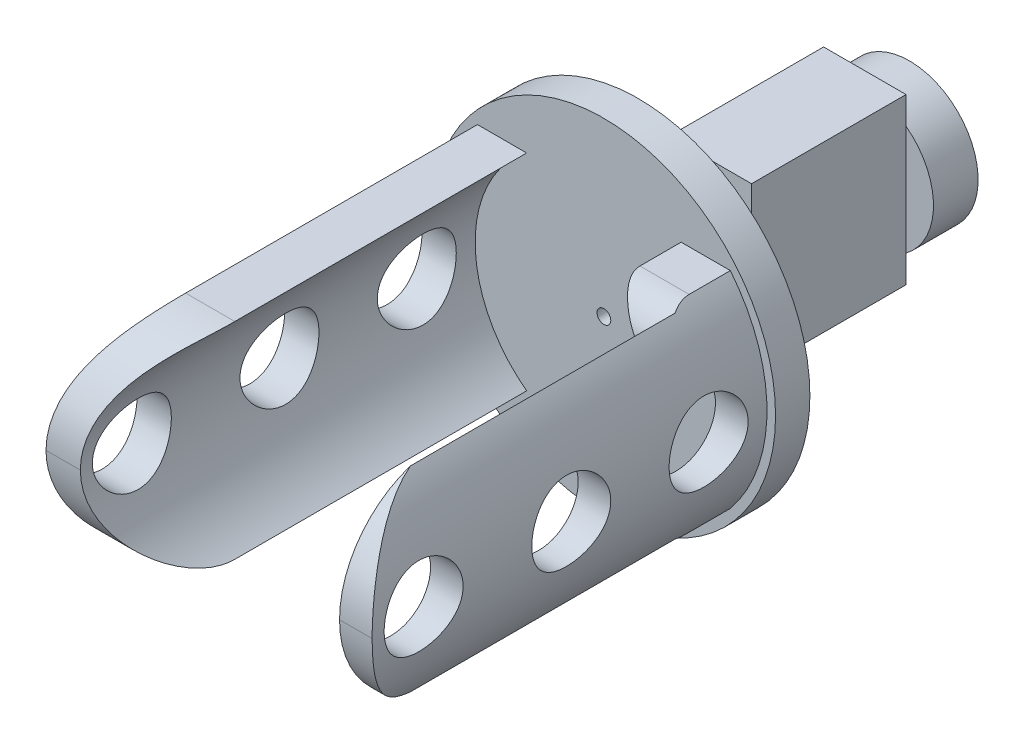
SolidWorks part; units mm, degrees
ref_plane "Plan de face" through (0, 0, 0) normal (0, 0, 1) x (1, 0, 0)
ref_plane "Plan de dessus" through (0, 0, 0) normal (0, 1, 0) x (1, 0, 0)
ref_plane "Plan de droite" through (0, 0, 0) normal (1, 0, 0) x (0, 0, -1)
sketch "Esquisse1" plane through (0, 0, 0) normal (0, 0, 1) x (1, 0, 0)
  circle A0 centre (0, 0) radius 50
  dimension "D1" = 100
extrude "Boss.-Extru.1" add sketch "Esquisse1" along normal blind 10
sketch "Esquisse2" plane through (0, 0, 0) normal (0, 0, -1) x (-1, 0, 0)
  circle A0 centre (0, 0) radius 47.5
  dimension "D1" = 95
extrude "Enlèv. mat.-Extru.1" cut sketch "Esquisse2" against normal blind 5
sketch "Esquisse6" plane through (0, 0, 10) normal (0, 0, 1) x (1, 0, 0)
  line L0 (0, 0) -> (0, 47.5) construction
  line L1 (0, 47.5) -> (0, -47.5) construction
  line L2 (-22.5, 30) -> (-22.5, -30) construction
  line L3 (-22.5, 30) -> (-36.8273, 30)
  line L4 (-22.5, -30) -> (-36.8273, -30)
  line L5 (22.5, -30) -> (36.8273, -30)
  line L6 (22.5, 30) -> (36.8273, 30)
  circle A0 centre (0, 0) radius 2
  circle A1 centre (0, 0) radius 47.5
  circle A2 centre (0, 0) radius 37.5
  circle A3 centre (0, 0) radius 50 construction
  dimension "D1" = 4
  dimension "D2" = 2.5
  dimension "D3" = 10
  dimension "D4" = 60
extrude "Boss.-Extru.4" add sketch "Esquisse6" along normal blind 115 contours A2 L3 A1 L4 | A2 L5 A1 L6 region at (-38.1648, 0, 10) region at (38.1648, 0, 10)
sketch "Esquisse7" plane through (0, 0, 5) normal (0, 0, -1) x (-1, 0, 0)
  circle A0 centre (0, 0) radius 2
  dimension "D1" = 4
extrude "Enlèv. mat.-Extru.2" cut sketch "Esquisse7" against normal blind 100
sketch "Esquisse12" plane through (0, 0, 10) normal (0, 0, 1) x (1, 0, 0)
  line L1 (-3.6437, 25.162) -> (0, 25.162)
  line L2 (-3.6437, 25.162) -> (-3.6437, 15.1247)
  line L3 (-3.6437, 15.1247) -> (0, 15.1247)
  line L4 (0, 25.162) -> (0, 15.1247)
extrude "Boss.-Extru.7" add sketch "Esquisse12" along normal blind 116
sketch "Esquisse14" plane through (0, 0, 0) normal (1, 0, 0) x (0, 0, -1)
  line L0 (-125, 0) -> (-10, 0) construction
  line L1 (-125, 30) -> (-125, -30) construction
  line L2 (-10, 50) -> (-10, -50) construction
  circle A0 centre (-110, 0) radius 11.5
  circle A2 centre (-67, 0) radius 11.5
  circle A3 centre (-27, 0) radius 11.5
  dimension "D4" = 23
  dimension "D5" = 23
  dimension "D6" = 23
  dimension "D1" = 100
  dimension "D2" = 17
  dimension "D3" = 40
extrude "Enlèv. mat.-Extru.3" cut sketch "Esquisse14" against normal through all both and the other way through all
sketch "Esquisse15" plane through (0, 0, 126) normal (0, 0, 1) x (1, 0, 0)
  line L1 (0, 15.1247) -> (-3.6437, 15.1247)
  line L2 (0, 15.1247) -> (0, 25.162)
  line L3 (0, 25.162) -> (-3.6437, 25.162)
  line L4 (-3.6437, 15.1247) -> (-3.6437, 25.162)
extrude "Enlèv. mat.-Extru.4" cut sketch "Esquisse15" against normal blind 116
sketch "Esquisse16" plane through (0, 0, 5) normal (0, 0, -1) x (-1, 0, 0)
  circle A0 centre (0, 0) radius 20
  circle A1 centre (0, 0) radius 2
  dimension "D1" = 40
extrude "Boss.-Extru.8" add sketch "Esquisse16" along normal blind 16
sketch "Esquisse17" plane through (0, 0, -11) normal (0, 0, -1) x (-1, 0, 0)
  line L0 (0, 0) -> (0, 20) construction
  line L1 (0, 20) -> (0, -20) construction
  line L2 (0, 0) -> (20, 0) construction
  line L3 (20, 0) -> (-20, 0) construction
  line L4 (0, 20) -> (1.98, 14.8687)
  line L5 (0, 20) -> (-1.98, 14.8687)
  line L6 (-0.9649, 14.9689) -> (-3.9011, 19.6158)
  line L7 (-3.9011, 19.6158) -> (-4.8485, 14.1948)
  line L8 (-3.9011, 19.6158) -> (0, 0) construction
  line L9 (0, 0) -> (3.9011, -19.6158) construction
  line L10 (-7.6524, 18.4781) -> (0, 0) construction
  line L11 (-11.1097, 16.6305) -> (0, 0) construction
  line L12 (-14.1402, 14.1441) -> (0, 0) construction
  line L13 (0, 0) -> (-16.6275, 11.1143) construction
  line L14 (0, 0) -> (-18.476, 7.6575) construction
  line L15 (0, 0) -> (-19.6148, 3.9065) construction
  line L16 (-9.9008, 11.2683) -> (-11.1097, 16.6305)
  line L17 (-11.1097, 16.6305) -> (-6.6069, 13.4666)
  line L18 (-11.2656, 9.9039) -> (-16.6275, 11.1143)
  line L19 (-16.6275, 11.1143) -> (-13.4647, 6.6107)
  line L20 (-14.9687, 0.9691) -> (-19.6148, 3.9065)
  line L21 (-19.6148, 3.9065) -> (-14.1934, 4.8524)
  line L22 (-7.6524, 18.4781) -> (-3.8597, 14.4949)
  line L23 (-7.6524, 18.4781) -> (-7.5184, 12.9797)
  line L24 (-14.1402, 14.1441) -> (-9.1121, 11.9151)
  line L25 (-14.1402, 14.1441) -> (-11.9126, 9.1154)
  line L26 (-18.476, 7.6575) -> (-14.4938, 3.8637)
  line L27 (-18.476, 7.6575) -> (-12.9777, 7.522)
  line L28 (-20, 0) -> (-14.8675, 1.9891)
  line L29 (-20, 0) -> (-14.8675, -1.9891)
  line L30 (-14.9687, -0.9691) -> (-19.6148, -3.9065)
  line L31 (-19.6148, -3.9065) -> (-14.1934, -4.8524)
  line L32 (-18.476, -7.6575) -> (-14.4938, -3.8637)
  line L33 (-18.476, -7.6575) -> (-12.9777, -7.522)
  line L34 (-16.6275, -11.1143) -> (-13.4647, -6.6107)
  line L35 (-11.2656, -9.9039) -> (-16.6275, -11.1143)
  line L36 (-14.1402, -14.1441) -> (-11.9126, -9.1154)
  line L37 (-14.1402, -14.1441) -> (-9.1121, -11.9151)
  line L38 (-9.9008, -11.2683) -> (-11.1097, -16.6305)
  line L39 (-11.1097, -16.6305) -> (-6.6069, -13.4666)
  line L40 (-7.6524, -18.4781) -> (-7.5184, -12.9797)
  line L41 (-7.6524, -18.4781) -> (-3.8597, -14.4949)
  line L42 (-3.9011, -19.6158) -> (-4.8485, -14.1948)
  line L43 (-0.9649, -14.9689) -> (-3.9011, -19.6158)
  line L44 (0, -20) -> (-1.98, -14.8687)
  line L45 (0, -20) -> (1.98, -14.8687)
  line L46 (0.9649, -14.9689) -> (3.9011, -19.6158)
  line L47 (3.9011, -19.6158) -> (4.8485, -14.1948)
  line L48 (7.6524, -18.4781) -> (3.8597, -14.4949)
  line L49 (7.6524, -18.4781) -> (7.5184, -12.9797)
  line L50 (11.1097, -16.6305) -> (6.6069, -13.4666)
  line L51 (9.9008, -11.2683) -> (11.1097, -16.6305)
  line L52 (14.1402, -14.1441) -> (9.1121, -11.9151)
  line L53 (14.1402, -14.1441) -> (11.9126, -9.1154)
  line L54 (11.2656, -9.9039) -> (16.6275, -11.1143)
  line L55 (16.6275, -11.1143) -> (13.4647, -6.6107)
  line L56 (18.476, -7.6575) -> (12.9777, -7.522)
  line L57 (18.476, -7.6575) -> (14.4938, -3.8637)
  line L58 (19.6148, -3.9065) -> (14.1934, -4.8524)
  line L59 (14.9687, -0.9691) -> (19.6148, -3.9065)
  line L60 (20, 0) -> (14.8675, -1.9891)
  line L61 (20, 0) -> (14.8675, 1.9891)
  line L62 (14.9687, 0.9691) -> (19.6148, 3.9065)
  line L63 (19.6148, 3.9065) -> (14.1934, 4.8524)
  line L64 (18.476, 7.6575) -> (14.4938, 3.8637)
  line L65 (18.476, 7.6575) -> (12.9777, 7.522)
  line L66 (16.6275, 11.1143) -> (13.4647, 6.6107)
  line L67 (11.2656, 9.9039) -> (16.6275, 11.1143)
  line L68 (14.1402, 14.1441) -> (11.9126, 9.1154)
  line L69 (14.1402, 14.1441) -> (9.1121, 11.9151)
  line L70 (9.9008, 11.2683) -> (11.1097, 16.6305)
  line L71 (11.1097, 16.6305) -> (6.6069, 13.4666)
  line L72 (7.6524, 18.4781) -> (7.5184, 12.9797)
  line L73 (7.6524, 18.4781) -> (3.8597, 14.4949)
  line L74 (3.9011, 19.6158) -> (4.8485, 14.1948)
  line L75 (0.9649, 14.9689) -> (3.9011, 19.6158)
  line L76 (0, 20) -> (1.98, 14.8687)
  circle A0 centre (0, 0) radius 20
  circle A1 centre (0, 0) radius 2
  circle A2 centre (0, 0) radius 15
  circle M45 centre (0, 0) radius 20
  dimension "D4" = 1.98
  dimension "D5" = 3.96
  dimension "D6" = 1.02
  dimension "D8" = 1.02
extrude "Enlèv. mat.-Extru.7" cut sketch "Esquisse17" against normal blind 16 contours L30 L29 M45 | L32 L31 M45 | L34 L33 M45 | L36 L35 M45 | L38 L37 M45 | L40 L39 M45 | L42 L41 M45 | L44 L43 M45 | L46 L45 M45 | L48 L47 M45 | L50 L49 M45 | L52 L51 M45 | L54 L53 M45 | L56 L55 M45 | L58 L57 M45 | L60 L59 M45 | L62 L61 M45 | L64 L63 M45 | L66 L65 M45 | L68 L67 M45 | L70 L69 M45 | L72 L71 M45 | L74 L73 M45 | L4 L75 M45 | L6 L5 M45 | L22 L7 M45 | L23 L17 M45 | L24 L16 M45 | L25 L18 M45 | L27 L19 M45 | L26 L21 M45 | L28 L20 M45 region at (-1.8282, 18.5572, -11) region at (1.8282, 18.5572, -11) region at (-5.4138, 17.8474, -11) region at (5.4138, 17.8474, -11) region at (-8.7896, 16.4494, -11) region at (8.7896, 16.4494, -11) region at (-11.8272, 14.4163, -11) region at (11.8272, 14.4163, -11) region at (-14.413, 11.8311, -11) region at (14.413, 11.8311, -11) region at (-16.447, 8.7941, -11) region at (16.447, 8.7941, -11) region at (-17.8459, 5.4187, -11) region at (17.8459, 5.4187, -11) region at (-18.5577, 1.832, -11) region at (18.5577, 1.832, -11) region at (-18.5577, -1.832, -11) region at (18.5577, -1.832, -11) region at (-17.8459, -5.4187, -11) region at (17.8459, -5.4187, -11) region at (-16.447, -8.7941, -11) region at (16.447, -8.7941, -11) region at (-14.413, -11.8311, -11) region at (14.413, -11.8311, -11) region at (-11.8272, -14.4163, -11) region at (11.8272, -14.4163, -11) region at (-8.7896, -16.4494, -11) region at (8.7896, -16.4494, -11) region at (-5.4138, -17.8474, -11) region at (5.4138, -17.8474, -11) region at (-1.8282, -18.5572, -11) region at (1.8282, -18.5572, -11)
fillet "Congé3" radius 30 4 edges at (29.6636, -30, 125) (-29.6636, -30, 125) (-29.6636, 30, 125) (29.6636, 30, 125)
sketch "Esquisse18" plane through (0, 0, 10) normal (0, 0, 1) x (1, 0, 0)
  line L0 (35, 0) -> (35, 35.7071)
  line L1 (35, 35.7071) -> (35, -35.7071)
  line L2 (35, -15) -> (37, -15)
  line L3 (35, 35.7071) -> (32, 35.7071)
  line L4 (35, 35.7071) -> (35, -35.7071)
  line L5 (35, -35.7071) -> (32, -35.7071)
  line L6 (32, 35.7071) -> (32, -35.7071)
  line L7 (35, 35.7071) -> (37, 35.7071)
  line L8 (35, 35.7071) -> (35, -35.7071)
  line L9 (35, -35.7071) -> (37, -35.7071)
  line L10 (37, 35.7071) -> (37, -35.7071)
  line L11 (35, 0) -> (37, 0)
  line L12 (35, 0) -> (35, 15)
  line L13 (35, 15) -> (37, 15)
  line L14 (37, 0) -> (37, 15)
  line L15 (37, 0) -> (32, 0)
  line L16 (32, 0) -> (34.5, 0)
  line L18 (38, -17) -> (31, -17)
  line L19 (38, -17) -> (38, 17)
  line L20 (38, 17) -> (31, 17)
  line L21 (31, -17) -> (31, 17)
  line L22 (38, -17) -> (31, 17) construction
  line L23 (38, 17) -> (31, -17) construction
  circle A0 centre (0, 0) radius 35
  circle A1 centre (0, 0) radius 50 construction
  arc M17 (22.5, -30) -> (22.5, 30) centre (0, 0) ccw
  dimension "D1" = 70
  dimension "D2" = 3
  dimension "D3" = 2
  dimension "D4" = 15
  dimension "D5" = 2.5
  dimension "D6" = 1
  dimension "D7" = 2
extrude "Enlèv. mat.-Extru.8" cut sketch "Esquisse18" along normal blind 150 contours L19 L20 L10 L18 M17 | L0 L11 L10 M17 | L13 L0 L10 M17 | L10 L20 L8 L13 | L11 L1 L10 M17 | L10 L1 L2 M17 | L18 L10 L2 L1 | L8 L20 L0 M17 | L18 L1 M17 region at (35.8843, -5.3474, 10) region at (35.8843, 5.3474, 10) region at (34.487, 15.8492, 10) region at (36.2519, 12.1846, 10) region at (36.2519, -12.1846, 10) region at (34.487, -15.8492, 10) region at (36, 16, 10) region at (37.5408, 0, 10) region at (36, -16, 10)
sketch "Esquisse21" plane through (38, 0, 0) normal (-1, 0, 0) x (0, 0, 1)
  line L0 (67, 0) -> (32, 0) construction
  line L1 (95, 30) -> (10, 30) construction
  line L2 (32, 30) -> (125, 30)
  line L3 (32, 30) -> (32, 0)
  line L4 (32, 0) -> (125, 0)
  line L5 (125, 30) -> (125, 0)
  line L7 (32, 0) -> (95, 0)
  line L8 (32, 0) -> (32, -30)
  line L9 (32, -30) -> (95, -30)
  line L10 (95, 0) -> (95, -30)
  line L11 (95, 0) -> (125, 0)
  line L12 (95, 0) -> (95, -30)
  line L13 (95, -30) -> (125, -30)
  line L14 (125, 0) -> (125, -30)
  line M2 (119.7184, 17) -> (10, 17)
  line M4 (10, -17) -> (119.7184, -17)
  arc M5 (119.7184, -17) -> (125, 0) centre (95, 0) ccw
  arc M6 (125, 0) -> (119.7184, 17) centre (95, 0) ccw
  circle M7 centre (110, 0) radius 11.5
  circle M8 centre (67, 0) radius 11.5
  circle M9 centre (27, 0) radius 11.5
  dimension "D1" = 35
extrude "Enlèv. mat.-Extru.9" cut sketch "Esquisse21" along normal blind 20 contours L5 L2 L3 M2 M6 | L4 L3 M9 M8 M7 M6 M2 | L10 L4 L8 M8 M9 M4 | L4 L10 M4 M5 M7 | L10 L8 L9 M4 | L14 L10 L13 M5 M4 region at (38, 23.2518, 79.5453) region at (38, 9.9625, 75.4364) region at (38, -8.7985, 123.3199) region at (38, -22.7664, 110.9241) region at (38, -0.6525, 47) region at (38, -23.5, 63.5)
fillet "Congé4" radius 10 2 edges at (29.6636, -30, 32) (29.6636, 30, 32)
sketch "Esquisse22" plane through (0, 0, -11) normal (0, 0, -1) x (-1, 0, 0)
  circle A0 centre (0, 0) radius 15
  dimension "D1" = 30
extrude "Boss.-Extru.9" add sketch "Esquisse22" along normal blind 10
sketch "Esquisse23" plane through (0, 0, -21) normal (0, 0, -1) x (-1, 0, 0)
  line L1 (-12, -24) -> (12, -24)
  line L2 (-12, -24) -> (-12, 24)
  line L3 (-12, 24) -> (12, 24)
  line L4 (12, -24) -> (12, 24)
  line L5 (-12, -24) -> (12, 24) construction
  line L6 (-12, 24) -> (12, -24) construction
  point P0 (0, 0)
  dimension "D1" = 48
  dimension "D2" = 24
extrude "Boss.-Extru.10" add sketch "Esquisse23" along normal blind 45
sketch "Esquisse24" plane through (0, 0, -66) normal (0, 0, -1) x (-1, 0, 0)
  circle A0 centre (0, 0) radius 20
extrude "Boss.-Extru.11" add sketch "Esquisse24" along normal blind 5
sketch "Esquisse25" plane through (0, 0, -71) normal (0, 0, -1) x (-1, 0, 0)
  circle A0 centre (0, 0) radius 20
  circle A1 centre (0, 0) radius 11.5
  dimension "D1" = 23
extrude "Boss.-Extru.12" add sketch "Esquisse25" along normal blind 8
